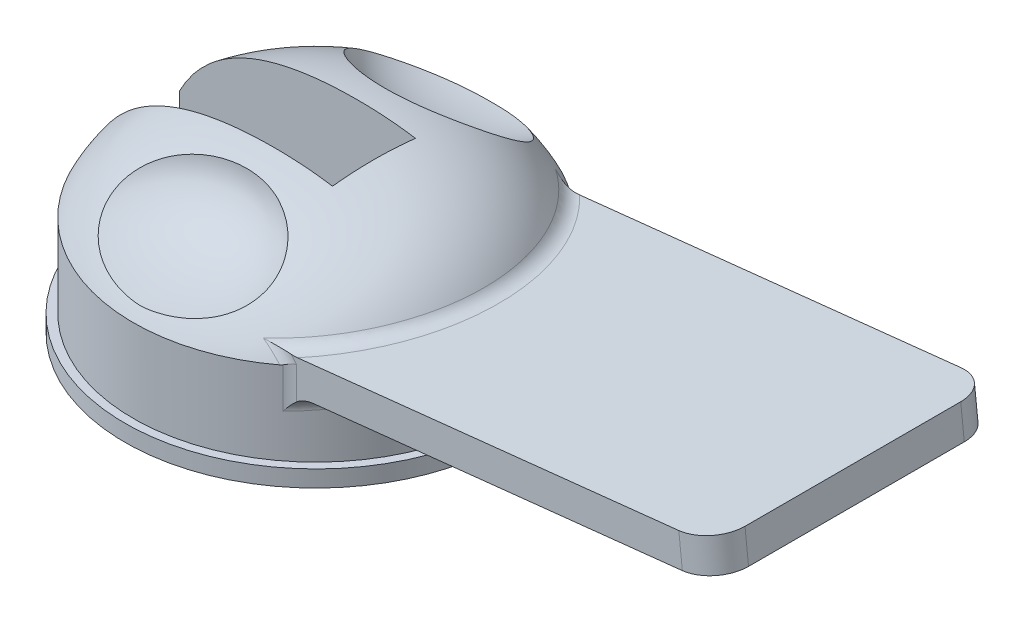
SolidWorks part; units mm, degrees
material "ABS"
ref_plane "Front Plane" through (0, 0, 0) normal (0, 0, 1) x (1, 0, 0)
ref_plane "Top Plane" through (0, 0, 0) normal (0, 1, 0) x (1, 0, 0)
ref_plane "Right Plane" through (0, 0, 0) normal (1, 0, 0) x (0, 0, -1)
sketch "Suction Cup Profile" plane through (0, 0, 0) normal (0, 0, 1) x (1, 0, 0)
  line L0 (0, 0) -> (0, 22) construction
  line L1 (0, 0) -> (-23, 0)
  line L2 (-23, 0) -> (-23, 2)
  line L3 (-23, 2) -> (-22, 2)
  line L4 (-22, 2) -> (-22, 12)
  line L5 (8.8234, 22) -> (-8.8234, 22) construction
  line L6 (0, 0) -> (0, 22)
  spline S0 degree 3 poles (-22, 12) (-18.4218, 19.0515) (-11.0292, 22) (0, 22) knots 0 0 0 0 1 1 1 1
  dimension "D1" = 23
  dimension "D2" = 2
  dimension "D3" = 1
  dimension "D4" = 10
  dimension "D5" = 22
revolve "Suction Cup Revolve" add sketch "Suction Cup Profile" angle 360 about L6
sketch "Lever Slot Profile" plane through (0, 0, 0) normal (0, 0, 1) x (1, 0, 0)
  line L0 (7, 10) -> (-20, 10)
  line L1 (-20, 10) -> (-20, 2)
  line L2 (23, 2) -> (-23, 2) construction
  line L3 (-20, 2) -> (-23, 2)
  line L4 (-23, 2) -> (-23, 26)
  line L5 (-23, 26) -> (7, 26)
  line L6 (7, 26) -> (7, 10)
  line L7 (-23, 0) -> (23, 0) construction
  line L8 (-22, 12) -> (-22, 2) construction
  dimension "D1" = 10
  dimension "D2" = 2
  dimension "D3" = 30
  dimension "D4" = 24
  dimension "D5" = 7
extrude "Lever Slot Cut" cut sketch "Lever Slot Profile" against normal blind 5 and the other way blind 5
fillet "Lever Slot Fillet" radius 1 3 edges at (7, 10, 0) (-20, 2, 0) (-20, 10, 0)
sketch "Cup Plunger Profile" plane through (0, 10, 0) normal (0, 1, 0) x (1, 0, 0)
  line L1 (3, 2) -> (-3, 2)
  line L2 (3, 2) -> (3, -2)
  line L3 (3, -2) -> (-3, -2)
  line L4 (-3, 2) -> (-3, -2)
  line L5 (3, 2) -> (-3, -2) construction
  line L6 (3, -2) -> (-3, 2) construction
  point P0 (0, 0)
  dimension "D1" = 4
  dimension "D2" = 6
extrude "Cup Plunger Cut" cut sketch "Cup Plunger Profile" against normal through all
sketch "Pad Slot Profile" plane through (0, 0, 0) normal (0, 0, 1) x (1, 0, 0)
  line L0 (0, 0) -> (0, 19.8107) construction
  line L1 (-20, 3) -> (-20, 9) construction
  line L2 (0, 9.5) -> (-17.5, 9.5)
  line L3 (0, 9.5) -> (0, -2.5)
  line L4 (0, -2.5) -> (-19.5, -2.5)
  line L5 (-19.5, 7.5) -> (-19.5, -2.5)
  line L6 (-19, 10) -> (6, 10) construction
  arc A0 (-19.5, 7.5) -> (-17.5, 9.5) centre (-17.5, 7.5) cw
  point P13 (-19.5, 9.5)
  dimension "D4" = 2
  dimension "D1" = 0.5
  dimension "D2" = 0.5
  dimension "D3" = 12
revolve "Pad Cut Profile" cut sketch "Pad Slot Profile" angle 360 about L0
sketch "Lever Profile" plane through (0, 0, 0) normal (0, 0, 1) x (1, 0, 0)
  line L0 (0, 0) -> (0, 25.9428) construction
  line L1 (0, 9) -> (65, 16) construction
  dimension "D1" = 9
  dimension "D2" = 65
  dimension "D3" = 16
ref_plane "Guide Plane 1" through (65, 16, 0) normal (0.9943, 0.1071, 0) x (0, 0, -1)
sketch "Lever Extension Profile" plane through (65, 16, 0) normal (0.9943, 0.1071, 0) x (0, 0, -1)
  line L0 (0, -8.9483) -> (0, 16.8454) construction
  line L1 (17, 2.6271) -> (-17, 2.6271)
  line L2 (17, 2.6271) -> (17, -1.3729)
  line L3 (17, -1.3729) -> (-17, -1.3729)
  line L4 (-17, 2.6271) -> (-17, -1.3729)
  line L5 (17, 2.6271) -> (-17, -1.3729) construction
  line L6 (17, -1.3729) -> (-17, 2.6271) construction
  ellipse E0 centre (0, 2.9828) end of major axis (-22, 2.9828) minor radius 2.3556 (-5, 5.2767) -> (5, 5.2767) ccw construction
  point P0 (0, 0.6271)
  dimension "D1" = 34
  dimension "D2" = 4
extrude "Lever Extension" add sketch "Lever Extension Profile" against normal up to next
fillet "Fillet Base" radius 2 6 edges at (13.9642, 10.5615, -17) (20.8211, 13.8846, -1.6625) (22, 9.9884, 0) (13.9642, 10.5615, 17)
fillet "Fillet Lever" radius 4 2 edges at (64.9328, 16.6235, 17) (64.9328, 16.6235, -17)
sketch "Ergonomic Finger Profile" plane through (0, 0, 0) normal (1, 0, 0) x (0, 0, -1)
  line L0 (8.3416, 21.906) -> (21.7873, 21.906)
  line L3 (21.7873, 21.906) -> (21.7873, 13.3782)
  spline S0 degree 3 poles (21.7873, 13.3782) (19.7598, 13.466) (13.2975, 14.1848) (8.2258, 17.6843) (8.3416, 21.906) knots 0.102846 0.102846 0.102846 0.102846 0.440696 1 1 1 1
revolve "Ergonomic Finger Cut" cut sketch "Ergonomic Finger Profile" angle 360 about L3
mirror "Ergonomic Finger Mirror" about plane through (0, 0, 0) normal (0, 0, 1) of "Ergonomic Finger Cut"
